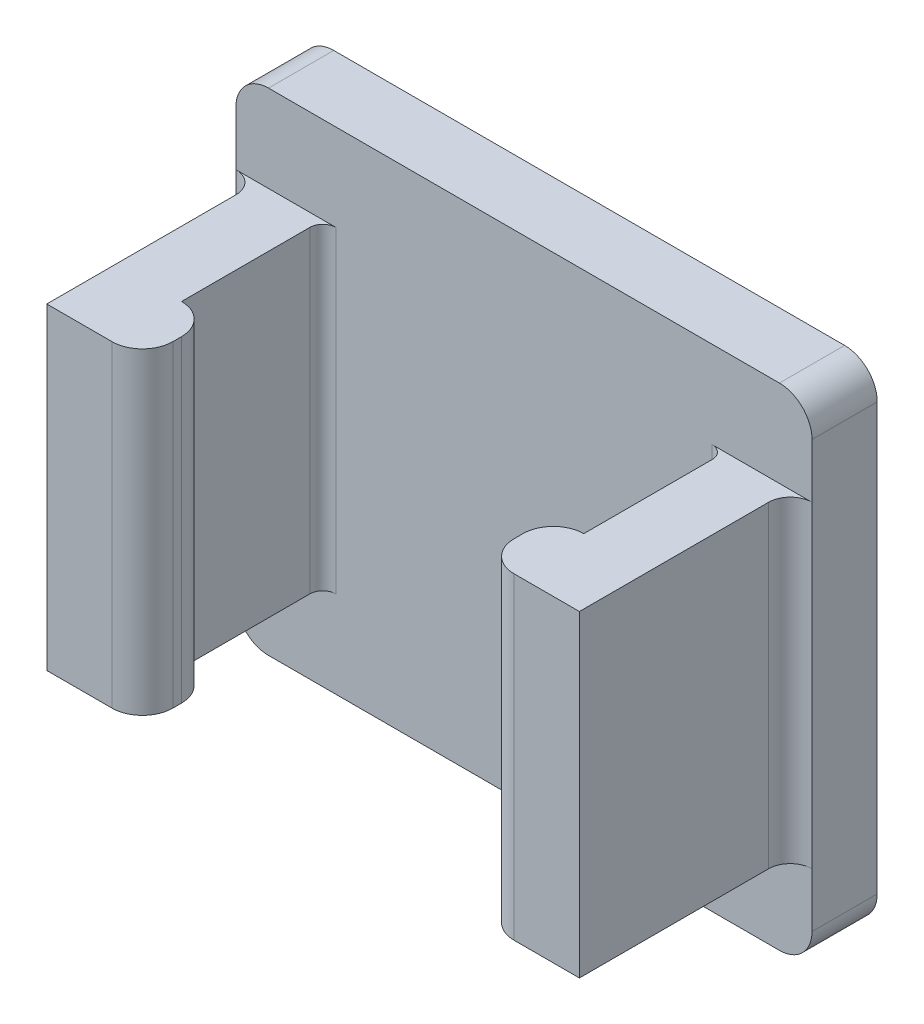
SolidWorks part; units mm, degrees
ref_plane "정면" through (0, 0, 0) normal (0, 0, 1) x (1, 0, 0)
ref_plane "윗면" through (0, 0, 0) normal (0, 1, 0) x (1, 0, 0)
ref_plane "우측면" through (0, 0, 0) normal (1, 0, 0) x (0, 0, -1)
sketch "스케치1" plane through (0, 0, 0) normal (0, 0, 1) x (1, 0, 0)
  line L1 (-6.125, -5.65) -> (6.125, -5.65)
  line L2 (-6.125, -5.65) -> (-6.125, 5.65)
  line L3 (-6.125, 5.65) -> (6.125, 5.65)
  line L4 (6.125, -5.65) -> (6.125, 5.65)
  line L5 (-6.125, -5.65) -> (6.125, 5.65) construction
  line L6 (-6.125, 5.65) -> (6.125, -5.65) construction
  point P0 (0, 0)
  dimension "D1" = 12.25
  dimension "D2" = 11.3
extrude "보스-돌출1" add sketch "스케치1" along normal blind 2.5
sketch "스케치2" plane through (0, 0, 2.5) normal (0, 0, 1) x (1, 0, 0)
  line L0 (-6.125, -5.65) -> (6.125, -5.65) construction
  line L1 (-6.125, 5.65) -> (-4.625, 5.65)
  line L2 (-6.125, 5.65) -> (-6.125, -5.65)
  line L3 (-6.125, -5.65) -> (-4.625, -5.65)
  line L4 (-4.625, 5.65) -> (-4.625, -5.65)
  line L6 (6.125, 5.65) -> (4.625, 5.65)
  line L7 (6.125, 5.65) -> (6.125, -5.65)
  line L8 (6.125, -5.65) -> (4.625, -5.65)
  line L9 (4.625, 5.65) -> (4.625, -5.65)
  dimension "D1" = 1.5
  dimension "D2" = 1.5
extrude "보스-돌출2" add sketch "스케치2" along normal blind 3.85
sketch "스케치5" plane through (0, 0, 2.5) normal (0, 0, 1) x (1, 0, 0)
  line L0 (4.625, 5.65) -> (4.625, -5.65) construction
  line L1 (-4.625, -5.75) -> (4.625, -5.75)
  line L2 (-4.625, -5.75) -> (-4.625, 5.75)
  line L3 (-4.625, 5.75) -> (4.625, 5.75)
  line L4 (4.625, -5.75) -> (4.625, 5.75)
  line L5 (-4.625, -5.75) -> (4.625, 5.75) construction
  line L6 (-4.625, 5.75) -> (4.625, -5.75) construction
  point P0 (0, 0)
  dimension "D1" = 11.5
extrude "컷-돌출1" cut sketch "스케치5" against normal blind 1
sketch "스케치8" plane through (-4.625, 0, 0) normal (1, 0, 0) x (0, 0, -1)
  line L0 (-6.35, -5.65) -> (-1.5, -5.65) construction
  line L1 (-6.35, 5.65) -> (-4.75, 5.65)
  line L2 (-6.35, 5.65) -> (-6.35, -5.65)
  line L3 (-6.35, -5.65) -> (-4.75, -5.65)
  line L4 (-4.75, 5.65) -> (-4.75, -5.65)
  dimension "D1" = 1.6
extrude "보스-돌출5" add sketch "스케치8" along normal blind 0.7
sketch "스케치9" plane through (4.625, 0, 0) normal (-1, 0, 0) x (0, 0, 1)
  line L0 (6.35, 5.65) -> (1.5, 5.65) construction
  line L1 (6.35, -5.65) -> (4.75, -5.65)
  line L2 (6.35, -5.65) -> (6.35, 5.65)
  line L3 (6.35, 5.65) -> (4.75, 5.65)
  line L4 (4.75, -5.65) -> (4.75, 5.65)
  dimension "D1" = 1.6
extrude "보스-돌출6" add sketch "스케치9" along normal blind 0.7
fillet "필렛8" radius 0.3 2 edges at (4.625, 0, 1.5) (-4.625, 0, 1.5)
sketch "스케치11" plane through (0, 5.65, 0) normal (0, 1, 0) x (1, 0, 0)
  line L0 (6.125, -6.35) -> (6.125, 0) construction
  line L1 (-6.125, -6.35) -> (6.125, -6.35)
  line L2 (-6.125, -6.35) -> (-6.125, -1.5)
  line L3 (-6.125, -1.5) -> (6.125, -1.5)
  line L4 (6.125, -6.35) -> (6.125, -1.5)
  line L5 (-4.325, -1.5) -> (4.325, -1.5) construction
  dimension "D1" = 0
extrude "컷-돌출2" cut sketch "스케치11" against normal blind 2
sketch "스케치12" plane through (0, -5.65, 0) normal (0, -1, 0) x (1, 0, 0)
  line L0 (6.125, 6.35) -> (6.125, 0) construction
  line L1 (-6.125, 6.35) -> (6.125, 6.35)
  line L2 (-6.125, 6.35) -> (-6.125, 1.5)
  line L3 (-6.125, 1.5) -> (6.125, 1.5)
  line L4 (6.125, 6.35) -> (6.125, 1.5)
  line L5 (4.325, 1.5) -> (-4.325, 1.5) construction
  dimension "D1" = 0
extrude "컷-돌출3" cut sketch "스케치12" against normal blind 2
sketch "스케치13" plane through (6.125, 0, 0) normal (1, 0, 0) x (0, 0, -1)
  line L1 (-1.5, 5.65) -> (0, 5.65)
  line L2 (-1.5, 5.65) -> (-1.5, -5.65)
  line L3 (-1.5, -5.65) -> (0, -5.65)
  line L4 (0, 5.65) -> (0, -5.65)
extrude "보스-돌출7" add sketch "스케치13" along normal blind 0.5
sketch "스케치14" plane through (-6.125, 0, 0) normal (-1, 0, 0) x (0, 0, 1)
  line L1 (1.5, 5.65) -> (0, 5.65)
  line L2 (1.5, 5.65) -> (1.5, -5.65)
  line L3 (1.5, -5.65) -> (0, -5.65)
  line L4 (0, 5.65) -> (0, -5.65)
extrude "보스-돌출8" add sketch "스케치14" along normal blind 0.5
fillet "필렛9" radius 0.5 2 edges at (6.125, 0, 1.5) (-6.125, 0, 1.5)
fillet "필렛10" radius 0.7 4 edges at (-3.925, 0, 6.35) (-3.925, 0, 4.75) (3.925, 0, 4.75) (3.925, 0, 6.35)
fillet "필렛11" radius 0.75 4 edges at (6.625, -5.65, 0.75) (-6.625, -5.65, 0.75) (-6.625, 5.65, 0.75) (6.625, 5.65, 0.75)
